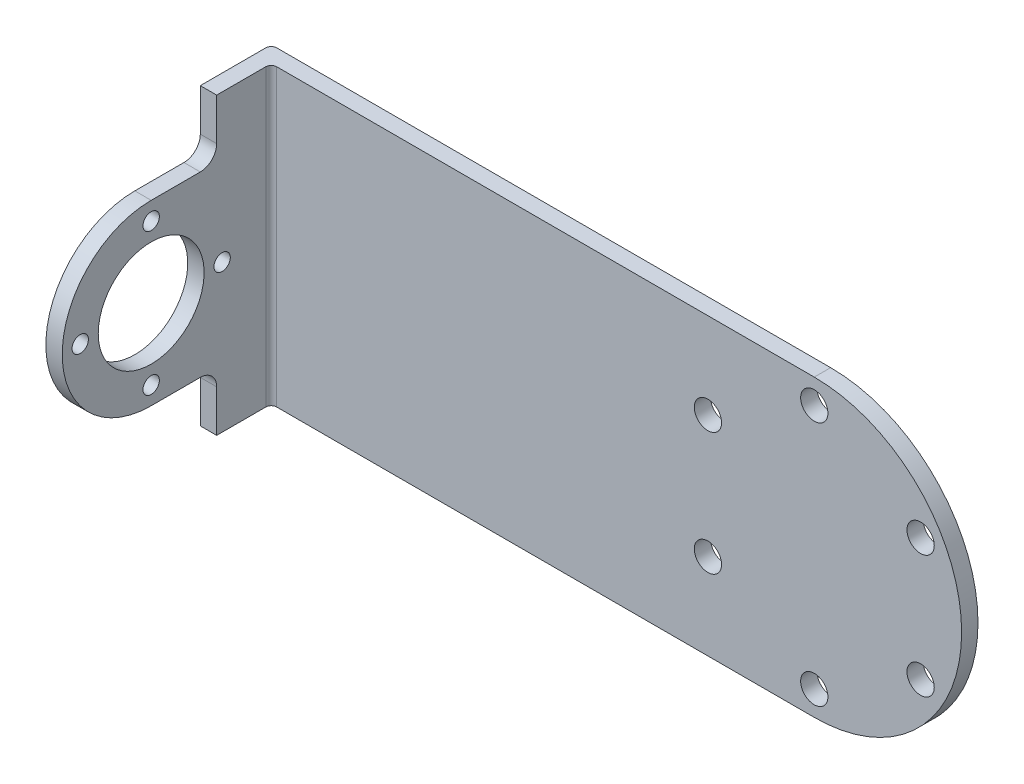
SolidWorks part; units mm, degrees
ref_plane "Front Plane" through (0, 0, 0) normal (0, 0, 1) x (1, 0, 0)
ref_plane "Top Plane" through (0, 0, 0) normal (0, 1, 0) x (1, 0, 0)
ref_plane "Right Plane" through (0, 0, 0) normal (1, 0, 0) x (0, 0, -1)
sketch "Sketch1" plane through (0, 0, 0) normal (0, 0, 1) x (1, 0, 0)
  line L0 (-102.5, 27) -> (0, 27)
  line L1 (-102.5, -27) -> (0, -27)
  line L3 (-102.5, 27) -> (-102.5, -27)
  line L5 (-103, 35) -> (-103, -35) construction
  circle A0 centre (19.4856, 11.25) radius 2.5
  circle A1 centre (19.4856, 11.25) radius 2.5 construction
  circle A2 centre (19.4856, -11.25) radius 2.5
  circle A3 centre (0, -22.5) radius 2.5
  circle A4 centre (-19.4856, -11.25) radius 2.5
  circle A5 centre (-19.4856, 11.25) radius 2.5
  circle A6 centre (0, 22.5) radius 2.5
  arc A7 (0, -27) -> (0, 27) centre (0, 0) ccw
  arc A8 (0, -28) -> (0, 28) centre (0, 0) ccw construction
  point P18 (0, 0)
  dimension "D2" = 1
  dimension "D3" = 0.5
  dimension "D1" = 6
extrude "Boss-Extrude1" add sketch "Sketch1" along normal blind 3 contours A7 L0 L3 L1 region at (-41.2274, 0, 0)
sketch "Sketch2" plane through (-102.5, 0, 0) normal (-1, 0, 0) x (0, 0, 1)
  line L0 (3, -27) -> (13, -27)
  line L1 (13, -27) -> (13, -19.3)
  line L2 (16, -16.3) -> (25, -16.3)
  line L3 (0, 0) -> (60, 0) construction
  line L4 (3, 27) -> (13, 27)
  line L5 (13, 27) -> (13, 19.3)
  line L6 (16, 16.3) -> (25, 16.3)
  line L7 (25, 9.7) -> (25, 16.3) construction
  arc A0 (25, -35) -> (25, 35) centre (25, 0) ccw construction
  arc A1 (25, -16.3) -> (25, 16.3) centre (25, 0) ccw
  circle A3 centre (25, 13) radius 1.5
  circle A4 centre (25, 13) radius 1.5 construction
  circle A5 centre (38, 0) radius 1.5
  circle A6 centre (25, -13) radius 1.5
  circle A7 centre (12, 0) radius 1.5
  circle A8 centre (25, 0) radius 9.7
  circle A10 centre (25, 0) radius 9.5 construction
  arc A11 (13, -19.3) -> (16, -16.3) centre (16, -19.3) cw
  arc A12 (13, 19.3) -> (16, 16.3) centre (16, 19.3) ccw
  point P15 (25, 13)
  point P34 (25, 0)
  point P37 (13, -16.3)
  point P40 (13, 16.3)
  line M7 (3, -27) -> (3, 27)
  dimension "D4" = 0.2
  dimension "D5" = 3
  dimension "D2" = 10
  dimension "D3" = 4
extrude "Boss-Extrude2" add sketch "Sketch2" against normal blind 3 contours L3 A7 A5 A1 L6 L5 L4 A3 M7 | L3 L0 L1 L2 A1 A5 A7 A6 M7 region at (-102.5, 0, 3.662)
fillet "Fillet1" radius 1 2 edges at (-99.5, 0, 3) (-102.5, 0, 0)
